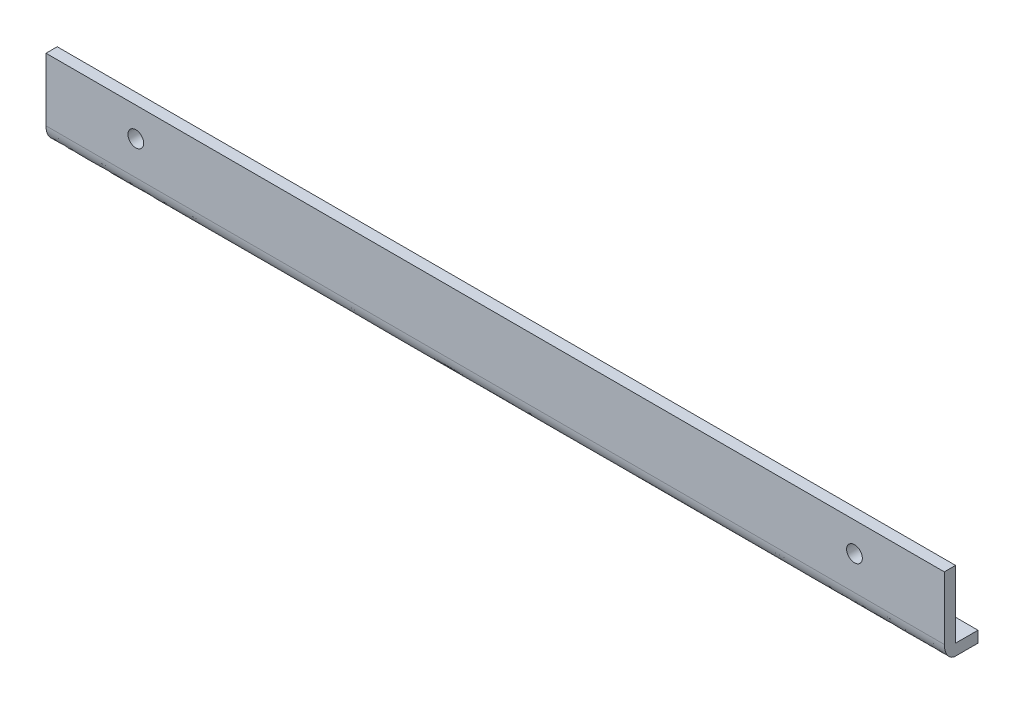
SolidWorks part; units mm, degrees
material "锻制不锈钢"
ref_plane "前视基准面" through (0, 0, 0) normal (0, 0, 1) x (1, 0, 0)
ref_plane "上视基准面" through (0, 0, 0) normal (0, 1, 0) x (1, 0, 0)
ref_plane "右视基准面" through (0, 0, 0) normal (1, 0, 0) x (0, 0, -1)
other "Configuration Table"
sketch "草图1" plane through (0, 0, 0) normal (0, 0, 1) x (1, 0, 0)
  line L0 (32.7044, 147.9193) -> (32.7044, 112.9193) construction
  line L1 (-167.2956, 147.9193) -> (232.7044, 147.9193)
  line L2 (-167.2956, 147.9193) -> (-167.2956, 112.9193)
  line L3 (-167.2956, 112.9193) -> (232.7044, 112.9193)
  line L4 (232.7044, 147.9193) -> (232.7044, 112.9193)
  circle A0 centre (-127.2956, 134.9193) radius 3.5
  circle A1 centre (192.7044, 134.9193) radius 3.5
  dimension "D3" = 7
  dimension "D1" = 400
  dimension "D2" = 35
  dimension "D4" = 40
  dimension "D5" = 13
extrude "凸台-拉伸1" add sketch "草图1" along normal blind 5
sketch "草图2" plane through (0, 0, 0) normal (0, 0, -1) x (-1, 0, 0)
  line L0 (-232.7044, 112.9193) -> (-232.7044, 147.9193) construction
  line L1 (-232.7044, 117.9193) -> (167.2956, 117.9193)
  line L2 (-232.7044, 117.9193) -> (-232.7044, 112.9193)
  line L3 (-232.7044, 112.9193) -> (167.2956, 112.9193)
  line L4 (167.2956, 117.9193) -> (167.2956, 112.9193)
  dimension "D1" = 5
extrude "凸台-拉伸2" add sketch "草图2" along normal blind 10
fillet "圆角1" radius 5 4 edges at (232.7044, 130.4193, 5) (232.7044, 112.9193, -2.5) (-167.2956, 112.9193, -2.5) (32.7044, 112.9193, 5)
